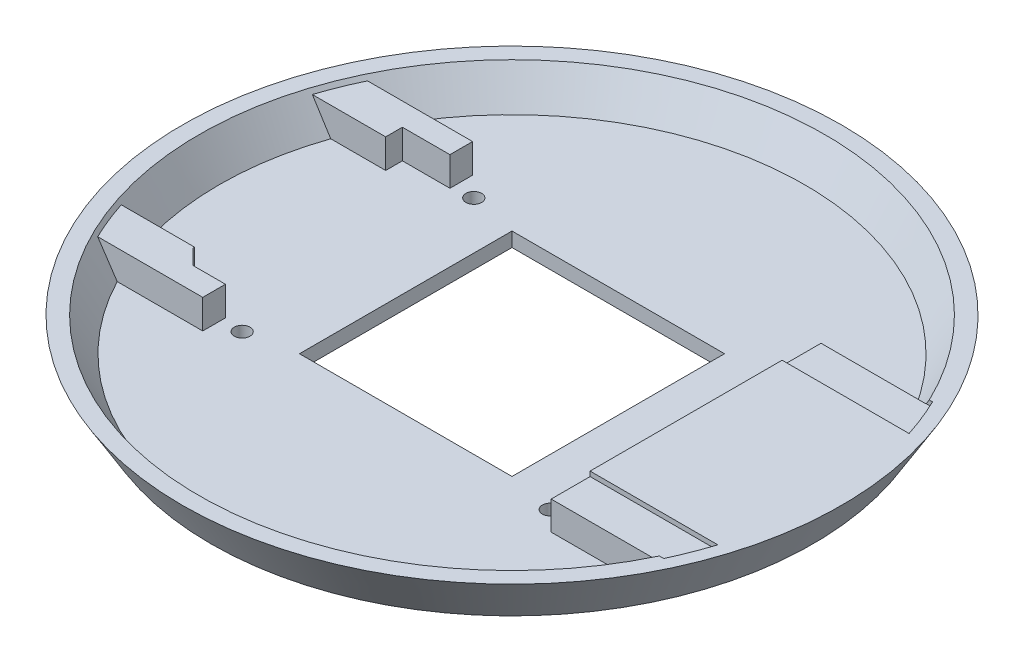
SolidWorks part; units mm, degrees
ref_plane "Front Plane" through (0, 0, 0) normal (0, 0, 1) x (1, 0, 0)
ref_plane "Top Plane" through (0, 0, 0) normal (0, 1, 0) x (1, 0, 0)
ref_plane "Right Plane" through (0, 0, 0) normal (1, 0, 0) x (0, 0, -1)
sketch "Sketch1" plane through (0, 0, 0) normal (0, 0, 1) x (1, 0, 0)
  line L0 (0, 0) -> (63, 0)
  line L1 (63, 0) -> (69, 10)
  line L6 (0, 3) -> (61.3014, 3)
  line L7 (61.3014, 3) -> (65.5014, 10)
  line L8 (69, 10) -> (65.5014, 10)
  line L9 (0, 0) -> (0, 3)
  line L10 (61.3014, 3) -> (66.4275, 11.5435) construction
  dimension "D1" = 69
  dimension "D2" = 63
  dimension "D3" = 10
  dimension "D4" = 3
revolve "Revolve1" add sketch "Sketch1" angle 360 about L9
sketch "Sketch2" plane through (0, 3, 0) normal (0, 1, 0) x (1, 0, 0)
  line L1 (-22.25, 22.25) -> (22.25, 22.25)
  line L2 (-22.25, 22.25) -> (-22.25, -22.25)
  line L3 (-22.25, -22.25) -> (22.25, -22.25)
  line L4 (22.25, 22.25) -> (22.25, -22.25)
  line L5 (-22.25, 22.25) -> (22.25, -22.25) construction
  line L6 (-22.25, -22.25) -> (22.25, 22.25) construction
  circle A0 centre (-32.25, 24.25) radius 1.65
  circle A1 centre (32.25, 24.25) radius 1.65
  circle A2 centre (-32.25, -24.25) radius 1.65
  circle A3 centre (32.25, -24.25) radius 1.65
  point P0 (0, 0)
  dimension "D3" = 3.3
  dimension "D5" = 10
  dimension "D6" = 10
  dimension "D7" = 10
  dimension "D9" = 2
  dimension "D10" = 2
  dimension "D11" = 2
  dimension "D1" = 44.5
  dimension "D2" = 44.5
  dimension "D4" = 10
  dimension "D8" = 2
  dimension "D12" = 0
  dimension "D13" = 0
extrude "Cut-Extrude1" cut sketch "Sketch2" against normal through all
sketch "Sketch4" plane through (0, 0, 0) normal (1, 0, 0) x (0, 0, -1)
  line L0 (69, 10) -> (-69, 10) construction
  line L1 (-28.25, 10) -> (28.25, 10)
  line L2 (-28.25, 10) -> (-28.25, 3)
  line L3 (-28.25, 3) -> (28.25, 3)
  line L4 (28.25, 10) -> (28.25, 3)
  line L5 (61.3014, 3) -> (-61.3014, 3) construction
  line L6 (28.25, 9.3) -> (28.25, 3) construction
  line L7 (-28.25, 3) -> (-28.25, 9.3) construction
  dimension "D1" = 0
  dimension "D2" = 0
  dimension "D3" = 0
extrude "Boss-Extrude1" add sketch "Sketch4" along normal up to next from offset 36.45
sketch "Sketch5" plane through (0, 10, 0) normal (0, 1, 0) x (1, 0, 0)
  line L0 (60.0162, -28.25) -> (36.45, -28.25)
  line L1 (36.45, -28.25) -> (36.45, -20.1)
  line L2 (36.45, -20.1) -> (63.1942, -20.1)
  line L3 (63.0344, 20.1) -> (36.45, 20.1)
  line L4 (36.45, 20.1) -> (36.45, 28.3)
  line L5 (36.45, 28.3) -> (59.7554, 28.3)
  line L6 (59.0963, -28.25) -> (36.45, -28.25) construction
  line L7 (59.514, 28.3) -> (-46.25, 28.3) construction
  line L8 (62.6955, 20.3) -> (-28.25, 20.3) construction
  line L9 (62.6955, -20.3) -> (-28.25, -20.3) construction
  line L10 (36.45, 28.25) -> (36.45, -28.25) construction
  arc A0 (63.0344, 20.1) -> (59.7554, 28.3) centre (0.25, -0.25) ccw
  arc A1 (60.0162, -28.25) -> (63.1942, -20.1) centre (0.25, -0.25) ccw
  dimension "D1" = 132
  dimension "D2" = 0
  dimension "D3" = 0
  dimension "D4" = 0.2
  dimension "D5" = 0.2
  dimension "D6" = 0
  dimension "D7" = 0
extrude "Cut-Extrude2" cut sketch "Sketch5" against normal blind 1
sketch "Sketch6" plane through (0, 0, 0) normal (1, 0, 0) x (0, 0, -1)
  line L0 (28.25, 9.3) -> (28.25, 3) construction
  line L1 (28.25, 9.1) -> (23.5, 9.1)
  line L2 (28.25, 9.1) -> (28.25, 3)
  line L3 (28.25, 3) -> (23.5, 3)
  line L4 (23.5, 9.1) -> (23.5, 3)
  line L5 (-28.25, 9.1) -> (-23.5, 9.1)
  line L6 (-28.25, 9.1) -> (-28.25, 3)
  line L7 (-28.25, 3) -> (-23.5, 3)
  line L8 (-23.5, 9.1) -> (-23.5, 3)
  line L9 (-28.25, 3) -> (-28.25, 9.3) construction
  line L10 (-28.25, 9.3) -> (28.25, 9.3) construction
  line L11 (-23.3, 9.3) -> (-23.3, 3) construction
  line L12 (23.3, 9.3) -> (23.3, 3) construction
  dimension "D1" = 3
  dimension "D2" = 3
  dimension "D3" = 0
  dimension "D4" = 0
  dimension "D5" = 0.2
  dimension "D6" = 0.2
  dimension "D7" = 0.2
  dimension "D8" = 0.2
extrude "Boss-Extrude2" add sketch "Sketch6" against normal up to next from offset 36.5 offset against normal yes
sketch "Sketch7" plane through (0, 0, 0) normal (0, 0, 1) x (1, 0, 0)
  line L0 (-58.6182, 3) -> (-46.45, 3)
  line L2 (-46.45, 9.1) -> (-46.45, 3)
  line L6 (-46.25, 3) -> (-46.25, 9.3) construction
  line L11 (-46.45, 9.1) -> (-60.5618, 9.1)
  line L19 (-58.6182, 3) -> (-62.5618, 9.1)
  line L20 (-62.5618, 9.1) -> (-60.5618, 9.1)
  dimension "D1" = 6.1
  dimension "D2" = 2
  dimension "D3" = 0.2
  dimension "D5" = 6.1
  dimension "D7" = 3.9437
extrude "Boss-Extrude3" add sketch "Sketch7" along normal up to surface (23.5 mm away) from offset 20 up to face at (-48.038, 6.8125, 23.5)
extrude "Boss-Extrude4" add sketch "Sketch7<2>" against normal up to surface (23.5 mm away) from offset 20 up to face at (-47.052, 5.2875, -23.5) offset against normal yes
sketch "Sketch7<2>" plane through (0, 0, 0) normal (0, 0, 1) x (1, 0, 0) same geometry as "Sketch7"
chamfer "Chamfer1" distance 3.2 angle 45 1 edges at (-46.45, 6.05, 23.5)
